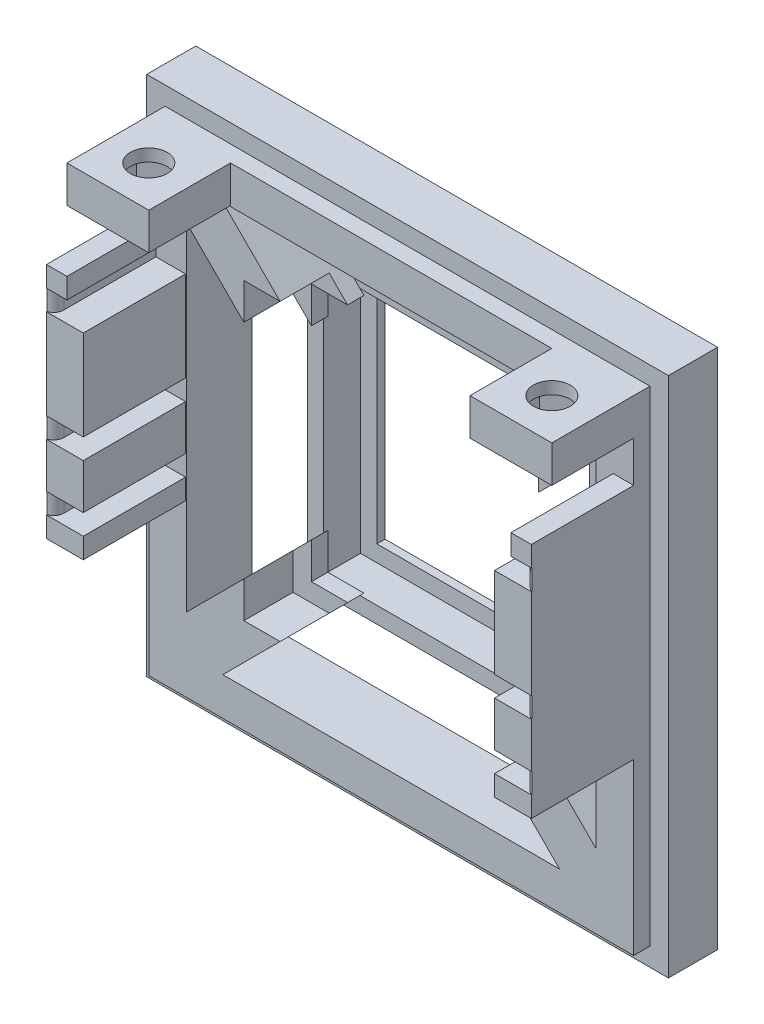
SolidWorks part; units mm, degrees
ref_plane "Plano frontal" through (0, 0, 0) normal (0, 0, 1) x (1, 0, 0)
ref_plane "Plano superior" through (0, 0, 0) normal (0, 1, 0) x (1, 0, 0)
ref_plane "Plano direito" through (0, 0, 0) normal (1, 0, 0) x (0, 0, -1)
sketch "Esboço3" plane through (0, 0, 0) normal (0, 0, 1) x (1, 0, 0)
  line L1 (23.7, 23.7) -> (-23.7, 23.7)
  line L2 (23.7, 23.7) -> (23.7, -23.7)
  line L3 (23.7, -23.7) -> (-23.7, -23.7)
  line L4 (-23.7, 23.7) -> (-23.7, -23.7)
  line L5 (23.7, 23.7) -> (-23.7, -23.7) construction
  line L6 (23.7, -23.7) -> (-23.7, 23.7) construction
  point P0 (0, 0)
  dimension "D1" = 47.4
  dimension "D2" = 47.4
extrude "Ressalto-extrusão2" add sketch "Esboço3" along normal blind 1.6
sketch "Esboço5" plane through (0, 0, 0) normal (0, 0, -1) x (-1, 0, 0)
  line L8 (25.5, -25.5) -> (25.5, 25.5)
  line L9 (25.5, 25.5) -> (-25.5, 25.5)
  line L10 (-25.5, 25.5) -> (-25.5, -25.5)
  line L11 (-25.5, -25.5) -> (25.5, -25.5)
  line L12 (25.5, -25.5) -> (25.5, 25.5)
  line L13 (25.5, 25.5) -> (-25.5, 25.5)
  line L14 (-25.5, 25.5) -> (-25.5, -25.5)
  line L15 (-25.5, -25.5) -> (25.5, -25.5)
  dimension "D1" = 1.8
extrude "Ressalto-extrusão3" add sketch "Esboço5" along normal blind 1.6
sketch "Esboço6" plane through (0, 0, -1.6) normal (0, 0, -1) x (-1, 0, 0)
  line L1 (3.5355, 0) -> (20, 16.4645)
  line L2 (-16.4645, -20) -> (0, -3.5355)
  line L3 (-20, 16.4645) -> (-3.5355, 0)
  line L4 (-20, -16.4645) -> (-3.5355, 0)
  line L5 (-16.4645, 20) -> (0, 3.5355)
  line L7 (16.4645, 20) -> (-16.4645, 20)
  line L8 (20, 16.4645) -> (20, -16.4645)
  line L9 (16.4645, -20) -> (-16.4645, -20)
  line L10 (-20, 16.4645) -> (-20, -16.4645)
  line L13 (3.5355, 0) -> (20, -16.4645)
  line L15 (0, 3.5355) -> (16.4645, 20)
  line L22 (0, -3.5355) -> (16.4645, -20)
  point P16 (0, 0)
extrude "Corte-extrusão1" cut sketch "Esboço6" against normal up to surface (3.2 mm away) up to face at (0, 0, 1.6)
sketch "Esboço7" plane through (0, 0, 1.6) normal (0, 0, 1) x (1, 0, 0)
  line L4 (-23.7, 23.7) -> (-23.7, -23.7)
  line L5 (-23.7, -23.7) -> (23.7, -23.7)
  line L6 (23.7, -23.7) -> (23.7, 23.7)
  line L7 (23.7, 23.7) -> (-23.7, 23.7)
  line L8 (-23.7, 16.1) -> (-23.7, -7.1)
  line L15 (-23.7, 23.7) -> (-15.7, 23.7)
  line L16 (-23.7, 23.7) -> (-23.7, 20.1)
  line L19 (-23.7, 20.1) -> (-15.7, 20.1)
  line L20 (-15.7, 23.7) -> (-15.7, 20.1)
  line L22 (-21.7, 14.1) -> (-23, 14.1)
  line L23 (-23, 14.1) -> (-23, 12.1)
  line L24 (-23, 12.1) -> (-20.1, 12.1)
  line L25 (23.7, 23.7) -> (-23.7, 23.7) construction
  line L26 (0, 0) -> (0, 31.8693) construction
  line L27 (-20.1, 3.3) -> (-23, 3.3)
  line L28 (-23, 3.3) -> (-23, 1.3)
  line L29 (-23, 1.3) -> (-20.1, 1.3)
  line L30 (-20.1, -3.1) -> (-23, -3.1)
  line L31 (-23, -3.1) -> (-23, -5.1)
  line L32 (-23, -5.1) -> (-20.1, -5.1)
  line L35 (-23.7, -3.807) -> (-20.1, -3.807)
  line L36 (-20.1, -7.1) -> (-20.1, -5.1)
  line L39 (-20.1, 12.1) -> (-20.1, 3.3)
  line L40 (-20.1, 1.3) -> (-20.1, -3.1)
  line L43 (-21.7, 16.1) -> (-21.7, 14.1)
  line L45 (-20.1, -7.1) -> (-23.7, -7.1)
  line L46 (-21.7, 16.1) -> (-23.7, 16.1)
  point P10 (-23, 13.1)
  point P23 (-21.55, 1.3)
  line M39 (-23.7, 23.7) -> (-23.7, -23.7)
  line M42 (23.7, 23.7) -> (-23.7, 23.7)
  dimension "D3" = 2
  dimension "D4" = 23
  dimension "D5" = 9.6
  dimension "D6" = 8.8
  dimension "D7" = 2
  dimension "D8" = 23
  dimension "D9" = 4.4
  dimension "D10" = 2
  dimension "D11" = 23
  dimension "D12" = 2
  dimension "D13" = 2
  dimension "D14" = 2
  dimension "D2" = 8
  dimension "D15" = 3.6
  dimension "D1" = 0
extrude "Ressalto-extrusão4" add sketch "Esboço7" along normal blind 10 contours L45 L36 L32 L31 L30 L40 L35 L8 | L35 L40 L29 L28 L27 L39 L24 L23 L22 M42 M39 region at (-22.0455, 5.6541, 1.6) region at (-22.0619, -5.9161, 1.6)
mirror "Espelhar1" about plane through (0, 0, 0) normal (1, 0, 0) of "Ressalto-extrusão4"
fillet "Filete1" radius 1 6 edges at (23, -4.1, 11.6) (-23, -4.1, 11.6) (-23, 2.3, 11.6) (23, 2.3, 11.6) (23, 13.1, 11.6) (-23, 13.1, 11.6)
sketch "Esboço10" plane through (0, 0, -1.6) normal (0, 0, -1) x (-1, 0, 0)
  line L0 (-16.4645, -20) -> (16.4645, -20) construction
  line L1 (0, -3.5355) -> (-16.4645, -20) construction
  line L2 (16.4645, -20) -> (0, -3.5355) construction
  line L3 (3.5355, 0) -> (20, -16.4645) construction
  line L4 (-25.5, -25.5) -> (25.5, -25.5)
  line L5 (25.5, -25.5) -> (25.5, 25.5)
  line L6 (25.5, 25.5) -> (-25.5, 25.5)
  line L7 (-25.5, 25.5) -> (-25.5, -25.5)
  line L8 (-25.5, -25.5) -> (25.5, -25.5)
  line L9 (25.5, -25.5) -> (25.5, 25.5)
  line L10 (25.5, 25.5) -> (-25.5, 25.5)
  line L11 (-25.5, 25.5) -> (-25.5, -25.5)
  line L12 (20, -16.4645) -> (20, 16.4645) construction
  line L13 (20, 16.4645) -> (3.5355, 0) construction
  line L14 (0, 3.5355) -> (16.4645, 20) construction
  line L15 (16.4645, 20) -> (-16.4645, 20) construction
  line L16 (-16.4645, 20) -> (0, 3.5355) construction
  line L17 (-3.5355, 0) -> (-20, 16.4645) construction
  line L18 (-20, 16.4645) -> (-20, -16.4645) construction
  line L19 (-20, -16.4645) -> (-3.5355, 0) construction
  line L20 (-16.4645, -20) -> (16.4645, -20)
  line L21 (0, -3.5355) -> (-16.4645, -20)
  line L22 (16.4645, -20) -> (0, -3.5355)
  line L23 (3.5355, 0) -> (20, -16.4645)
  line L24 (20, -16.4645) -> (20, 16.4645)
  line L25 (20, 16.4645) -> (3.5355, 0)
  line L26 (0, 3.5355) -> (16.4645, 20)
  line L27 (16.4645, 20) -> (-16.4645, 20)
  line L28 (-16.4645, 20) -> (0, 3.5355)
  line L29 (-3.5355, 0) -> (-20, 16.4645)
  line L30 (-20, 16.4645) -> (-20, -16.4645)
  line L31 (-20, -16.4645) -> (-3.5355, 0)
  dimension "D1" = 0
extrude "Ressalto-extrusão5" add sketch "Esboço10" along normal blind 3.2
sketch "Esboço11" plane through (0, 0, 1.6) normal (0, 0, 1) x (1, 0, 0)
  line L1 (14.4, 14.4) -> (-14.4, 14.4)
  line L2 (14.4, 14.4) -> (14.4, -14.4)
  line L3 (14.4, -14.4) -> (-14.4, -14.4)
  line L4 (-14.4, 14.4) -> (-14.4, -14.4)
  line L5 (14.4, 14.4) -> (-14.4, -14.4) construction
  line L6 (14.4, -14.4) -> (-14.4, 14.4) construction
  point P0 (0, 0)
  dimension "D1" = 28.8
  dimension "D2" = 28.8
extrude "Corte-extrusão2" cut sketch "Esboço11" against normal blind 4.8
sketch "Esboço14" plane through (0, 0, -3.2) normal (0, 0, 1) x (1, 0, 0)
  line L1 (12.6, 12.6) -> (-12.6, 12.6)
  line L2 (12.6, 12.6) -> (12.6, -12.6)
  line L3 (12.6, -12.6) -> (-12.6, -12.6)
  line L4 (-12.6, 12.6) -> (-12.6, -12.6)
  line L5 (12.6, 12.6) -> (-12.6, -12.6) construction
  line L6 (12.6, -12.6) -> (-12.6, 12.6) construction
  point P0 (0, 0)
  dimension "D1" = 25.2
  dimension "D2" = 25.2
extrude "Corte-extrusão4" cut sketch "Esboço14" against normal through all
sketch "Esboço15" plane through (0, 0, 1.6) normal (0, 0, 1) x (1, 0, 0)
  line L0 (0, 0) -> (0, -28.3802) construction
  line L1 (-23.7, -23.7) -> (23.7, -23.7) construction
  line L2 (17.4, -12.9) -> (-17.4, -12.9)
  line L3 (17.4, -12.9) -> (17.4, -23.7)
  line L4 (17.4, -23.7) -> (-17.4, -23.7)
  line L5 (-17.4, -12.9) -> (-17.4, -23.7)
  line L6 (17.4, -12.9) -> (-17.4, -23.7) construction
  line L7 (17.4, -23.7) -> (-17.4, -12.9) construction
  point P3 (0, -18.3)
  dimension "D1" = 34.8
  dimension "D2" = 10.8
extrude "Ressalto-extrusão7" add sketch "Esboço7<3>" along normal blind 8 contours L20 L19 M42 M39 region at (-19.7, 21.9, 1.6)
sketch "Esboço7<3>" plane through (0, 0, 1.6) normal (0, 0, 1) x (1, 0, 0) same geometry as "Esboço7"
mirror "Espelhar2" about plane through (0, 0, 0) normal (1, 0, 0) of "Ressalto-extrusão7"
sketch "Esboço18" plane through (0, 20.1, 0) normal (0, -1, 0) x (1, 0, 0)
  line L0 (-15.7, 5.6) -> (30.1273, 5.6) construction
  line L2 (0, -9.02) -> (0, 9.02) construction
  line L3 (-19.7, 8.8332) -> (-22.5, 7.2166)
  line L4 (-22.5, 7.2166) -> (-22.5, 3.9834)
  line L5 (-22.5, 3.9834) -> (-19.7, 2.3668)
  line L6 (-19.7, 2.3668) -> (-16.9, 3.9834)
  line L7 (-16.9, 3.9834) -> (-16.9, 7.2166)
  line L8 (-16.9, 7.2166) -> (-19.7, 8.8332)
  line L9 (16.9, 7.2166) -> (19.7, 8.8332)
  line L10 (16.9, 3.9834) -> (16.9, 7.2166)
  line L11 (19.7, 2.3668) -> (16.9, 3.9834)
  line L12 (22.5, 3.9834) -> (19.7, 2.3668)
  line L13 (22.5, 7.2166) -> (22.5, 3.9834)
  line L14 (19.7, 8.8332) -> (22.5, 7.2166)
  circle A0 centre (-19.7, 5.6) radius 2.8 construction
  circle A1 centre (-19.7, 5.6) radius 1.8
  circle A2 centre (19.7, 5.6) radius 2.8 construction
  circle A3 centre (19.7, 5.6) radius 1.8
  dimension "D2" = 3.6
  dimension "D1" = 5.6
extrude "Corte-extrusão8" cut sketch "Esboço18" against normal blind 2.4 contours L7 L8 L3 L4 L5 L6 A1 | L9 L14 L13 L12 L11 L10 region at (-18.3428, 20.1, 7.9508)
extrude "Corte-extrusão9" cut sketch "Esboço18<3>" against normal through all contours A3 | A1 region at (-19.7, 20.1, 5.6) region at (19.7, 20.1, 5.6)
sketch "Esboço18<3>" plane through (0, 20.1, 0) normal (0, -1, 0) x (1, 0, 0) same geometry as "Esboço18"
sketch "Esboço19" plane through (0, 0, -4.8) normal (0, 0, -1) x (-1, 0, 0)
  line L0 (-13, 13) -> (-13, -13)
  line L1 (-12.6, 12.6) -> (12.6, 12.6)
  line L2 (-12.6, 12.6) -> (-12.6, -12.6)
  line L3 (-12.6, -12.6) -> (12.6, -12.6)
  line L4 (12.6, 12.6) -> (12.6, -12.6)
  line L5 (-13, -13) -> (13, -13)
  line L6 (13, 13) -> (13, -13)
  line L7 (-13, 13) -> (13, 13)
  line L8 (-14.6, 14.6) -> (-14.6, -14.6)
  line L9 (-14.6, -14.6) -> (14.6, -14.6)
  line L10 (14.6, 14.6) -> (14.6, -14.6)
  line L11 (-14.6, 14.6) -> (14.6, 14.6)
  line M10 (12.6, 9.0645) -> (20, 16.4645)
  line M12 (20, -16.4645) -> (12.6, -9.0645)
  line M15 (9.0645, -12.6) -> (16.4645, -20)
  line M17 (-16.4645, -20) -> (-9.0645, -12.6)
  line M20 (-12.6, -9.0645) -> (-20, -16.4645)
  line M22 (-20, 16.4645) -> (-12.6, 9.0645)
  line M25 (-9.0645, 12.6) -> (-16.4645, 20)
  line M27 (16.4645, 20) -> (9.0645, 12.6)
  dimension "D1" = 0.4
  dimension "D2" = 1.6
extrude "Ressalto-extrusão8" add sketch "Esboço19" along normal blind 3.6 separate body contours L11 L8 L0 L7 M22 M25 | L8 L0 M22 M20 | L11 L7 M25 M27 | L11 L7 L6 L10 M27 M10 | L10 L6 M10 M12 | L10 L6 L5 L9 M12 M15 | L9 L5 M17 M15 | L8 L9 L5 L0 M17 M20 region at (13.0726, 11.2322, -4.8) region at (13.8208, 0, -4.8) region at (0, 13.8208, -4.8) region at (13.0726, -11.2322, -4.8) region at (-10.3158, 13.7486, -4.8) region at (0, -13.8208, -4.8) region at (-13.8208, 0, -4.8) region at (-11.2322, -13.0726, -4.8)
sketch "Esboço20" plane through (0, 0, -8.4) normal (0, 0, -1) x (-1, 0, 0)
  line L0 (-14.6, -14.6) -> (14.6, -14.6) construction
  line L1 (14.6, 14.6) -> (14.6, -14.6) construction
  line L2 (-14.6, 14.6) -> (14.6, 14.6) construction
  line L3 (-14.6, 14.6) -> (-14.6, -14.6) construction
  line L4 (-14.6, -14.6) -> (14.6, -14.6)
  line L5 (14.6, 14.6) -> (14.6, -14.6)
  line L6 (-14.6, 14.6) -> (14.6, 14.6)
  line L7 (-14.6, 14.6) -> (-14.6, -14.6)
  line L8 (-11.4, -11.4) -> (11.4, -11.4)
  line L9 (11.4, 11.4) -> (11.4, -11.4)
  line L10 (-11.4, 11.4) -> (11.4, 11.4)
  line L11 (-11.4, 11.4) -> (-11.4, -11.4)
  dimension "D1" = 3.2
extrude "Ressalto-extrusão9" add sketch "Esboço20" along normal blind 0.8
fillet "Filete2" radius 2 8 edges at (0, -14.6, -9.2) (14.6, 0, -9.2) (0, 14.6, -9.2) (-14.6, 0, -9.2) (-14.6, -14.6, -7) (-14.6, 14.6, -7) (14.6, -14.6, -7) (14.6, 14.6, -7)
